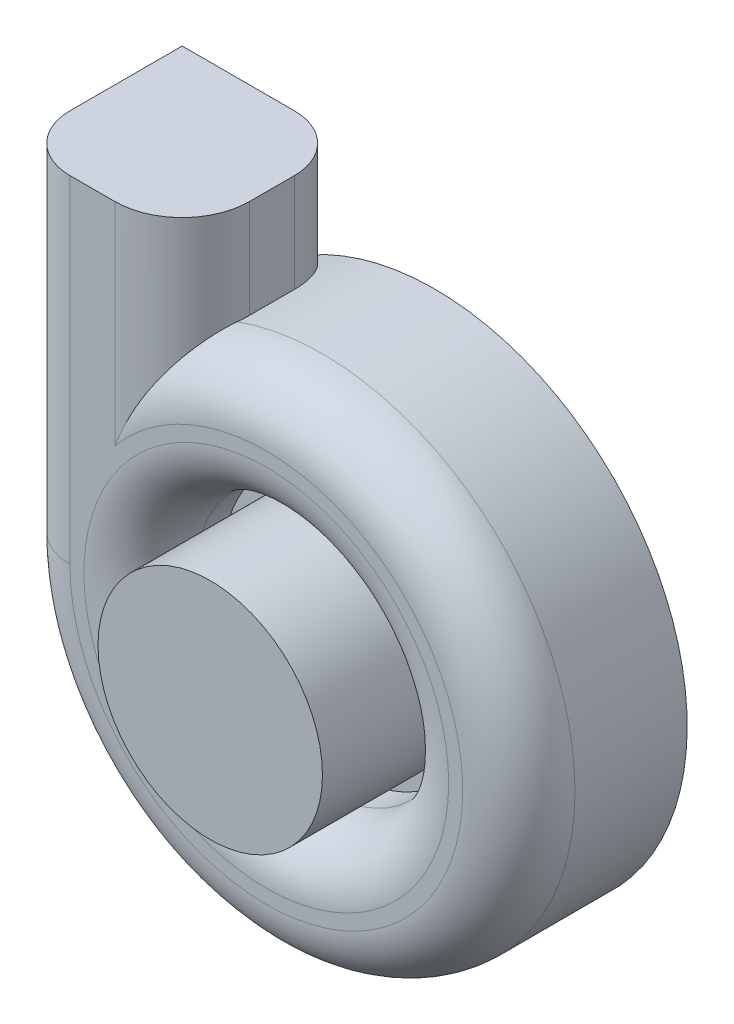
SolidWorks part; units mm, degrees
ref_plane "Front Plane" through (0, 0, 0) normal (0, 0, 1) x (1, 0, 0)
ref_plane "Top Plane" through (0, 0, 0) normal (0, 1, 0) x (1, 0, 0)
ref_plane "Right Plane" through (0, 0, 0) normal (1, 0, 0) x (0, 0, -1)
sketch "Sketch2" plane through (0, 0, 0) normal (0, 0, 1) x (1, 0, 0)
  line L2 (-45, 0) -> (-45, 60)
  line L3 (-45, 60) -> (-15, 60)
  line L4 (-15, 42.4264) -> (-15, 60)
  arc A0 (-45, 0) -> (-15, 42.4264) centre (0, 0) ccw
  dimension "D1" = 90
  dimension "D2" = 60
  dimension "D3" = 30
extrude "Boss-Extrude1" add sketch "Sketch2" along normal blind 30
sketch "Sketch3" plane through (0, 0, 30) normal (0, 0, 1) x (1, 0, 0)
  circle A0 centre (0, 0) radius 22.5
  dimension "D1" = 45
extrude "Cut-Extrude1" cut sketch "Sketch3" against normal blind 15
fillet "Fillet1" radius 10 3 edges at (-45, 30, 30) (22.5, 0, 30) (36.7423, -25.9808, 30)
sketch "Sketch4" plane through (0, 0, 15) normal (0, 0, 1) x (1, 0, 0)
  circle A0 centre (0, 0) radius 20
  dimension "D1" = 40
extrude "Boss-Extrude2" add sketch "Sketch4" along normal blind 25
fillet "Fillet2" radius 10 1 edges at (-15, 51.2132, 0)
fillet "Fillet3" radius 12 1 edges at (-15, 45.8114, 30)
